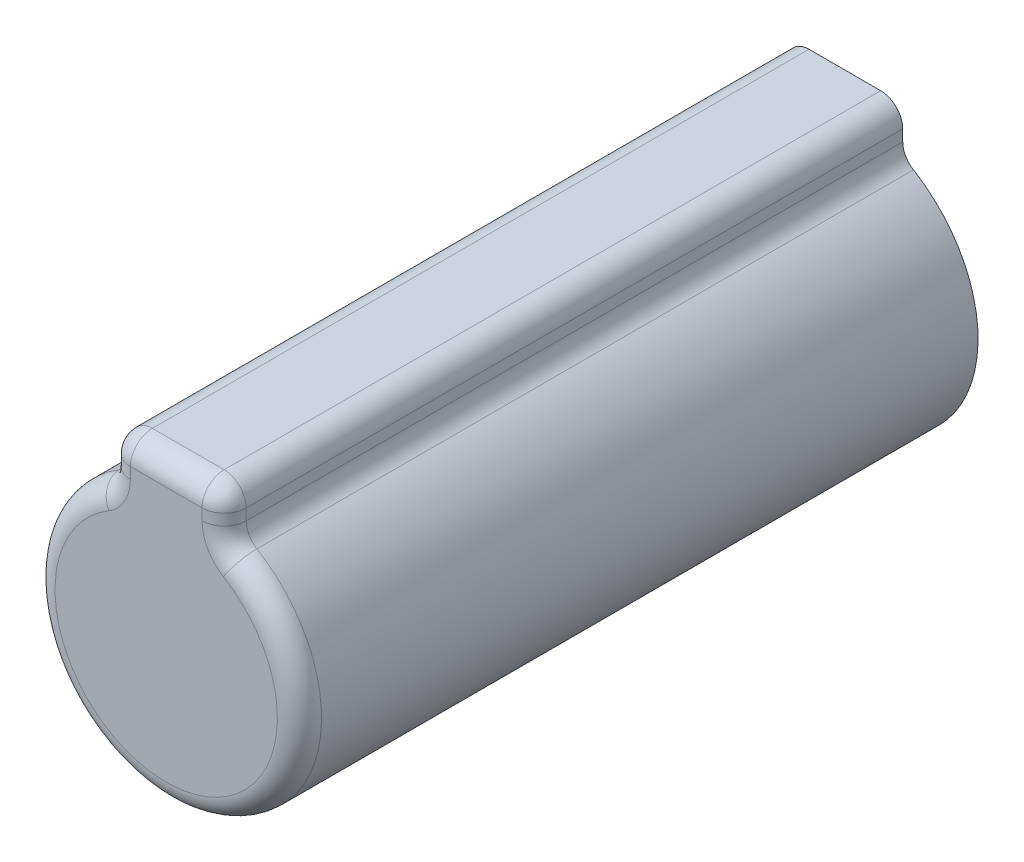
SolidWorks part; units mm, degrees
ref_plane "Front Plane" through (0, 0, 0) normal (0, 0, 1) x (1, 0, 0)
ref_plane "Top Plane" through (0, 0, 0) normal (0, 1, 0) x (1, 0, 0)
ref_plane "Right Plane" through (0, 0, 0) normal (1, 0, 0) x (0, 0, -1)
sketch "Sketch1" plane through (0, 0, 0) normal (0, 0, 1) x (1, 0, 0)
  line L1 (-7.5, 27.15) -> (7.5, 27.15)
  line L2 (-7.5, 27.15) -> (-7.5, 19.7756)
  line L4 (7.5, 27.15) -> (7.5, 19.7756)
  arc A0 (-7.5, 19.7756) -> (7.5, 19.7756) centre (0, 0) ccw
  point P3 (0, 21.15)
  dimension "D1" = 42.3
  dimension "D2" = 15
  dimension "D3" = 27.15
  dimension "D4" = 7.5
extrude "Extrude-Thin1" add sketch "Sketch1" along normal blind 120 thin thin type one direction wall 3
fillet "Fillet1" radius 4 8 edges at (-7.5, 19.7756, 60) (7.5, 19.7756, 60) (7.5, 27.15, 60) (-7.5, 27.15, 60) (10.5, 30.15, 60) (-10.5, 30.15, 60) (-10.5, 21.7479, 60) (10.5, 21.7479, 60)
sketch "Sketch2" plane through (0, 0, 120) normal (0, 0, 1) x (1, 0, 0)
  line L3 (10.5, 24.1283) -> (10.5, 26.15)
  line L4 (6.5, 30.15) -> (-6.5, 30.15)
  line L5 (-10.5, 26.15) -> (-10.5, 24.1283)
  line L6 (10.5, 24.1283) -> (10.5, 26.15)
  line L7 (6.5, 30.15) -> (-6.5, 30.15)
  line L8 (-10.5, 26.15) -> (-10.5, 24.1283)
  arc A5 (10.5, 26.15) -> (6.5, 30.15) centre (6.5, 26.15) ccw
  arc A6 (-6.5, 30.15) -> (-10.5, 26.15) centre (-6.5, 26.15) ccw
  arc A7 (-12.4396, 20.6997) -> (-10.5, 24.1283) centre (-14.5, 24.1283) ccw
  arc A8 (-12.4396, 20.6997) -> (12.4396, 20.6997) centre (0, 0) ccw
  arc A9 (10.5, 24.1283) -> (12.4396, 20.6997) centre (14.5, 24.1283) ccw
  arc A10 (10.5, 26.15) -> (6.5, 30.15) centre (6.5, 26.15) ccw
  arc A11 (-6.5, 30.15) -> (-10.5, 26.15) centre (-6.5, 26.15) ccw
  arc A12 (-12.4396, 20.6997) -> (-10.5, 24.1283) centre (-14.5, 24.1283) ccw
  arc A13 (-12.4396, 20.6997) -> (12.4396, 20.6997) centre (0, 0) ccw
  arc A14 (10.5, 24.1283) -> (12.4396, 20.6997) centre (14.5, 24.1283) ccw
  dimension "D1" = 0
extrude "Boss-Extrude1" add sketch "Sketch2" along normal blind 3
fillet "Fillet2" radius 4 8 edges at (0, -24.15, 123) (-11.0185, 22.1587, 123) (-10.5, 25.1391, 123) (-9.3284, 28.9784, 123) (0, 30.15, 123) (9.3284, 28.9784, 123) (10.5, 25.1391, 123) (11.0185, 22.1587, 123)
